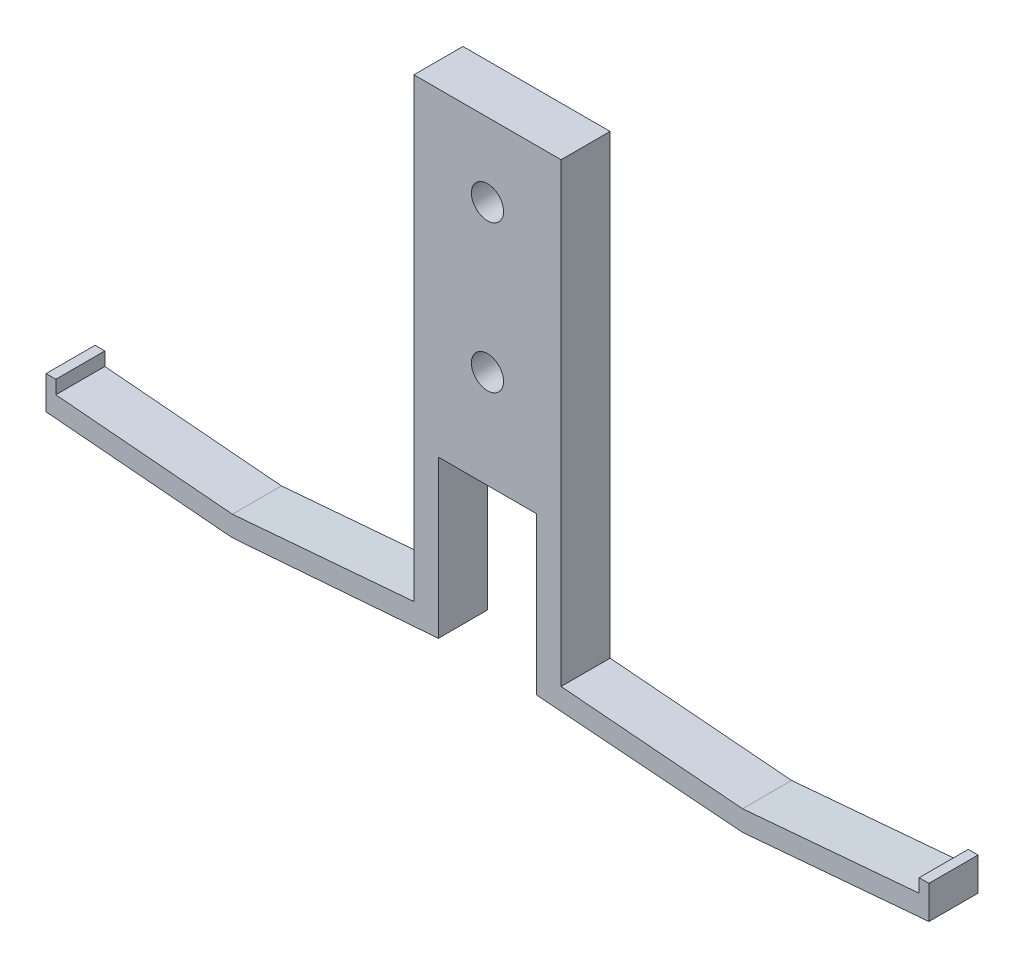
SolidWorks part; units mm, degrees
material "Nylon 6/10"
ref_plane "Front Plane" through (0, 0, 0) normal (0, 0, 1) x (1, 0, 0)
ref_plane "Top Plane" through (0, 0, 0) normal (0, 1, 0) x (1, 0, 0)
ref_plane "Right Plane" through (0, 0, 0) normal (1, 0, 0) x (0, 0, -1)
sketch "Sketch2" plane through (0, 0, 0) normal (0, 0, 1) x (1, 0, 0)
  line L1 (12.7, 0) -> (12.7, -40.64)
  line L2 (12.7, -40.64) -> (66.04, -44.7734)
  line L3 (66.04, -44.7734) -> (114.3, -40.64)
  line L4 (114.3, -40.64) -> (114.3, -32.0734)
  line L5 (111.76, -32.0734) -> (111.76, -35.56)
  line L6 (111.76, -35.56) -> (66.04, -39.4758)
  line L19 (114.3, -32.0734) -> (111.76, -32.0734)
  line L20 (0, 125.2351) -> (0, -75.9356) construction
  line L21 (12.7, 0) -> (-12.7, 0)
  line L22 (0, 0) -> (0, 82.55)
  line L23 (19.05, 82.55) -> (-19.05, 82.55)
  line L24 (19.05, 82.55) -> (19.05, 0)
  line L25 (19.05, 0) -> (19.05, -35.56)
  line L26 (19.05, -35.56) -> (66.04, -39.4758)
  line L27 (-19.05, 0) -> (-19.05, -35.56)
  line L28 (-19.05, 82.55) -> (-19.05, 0)
  line L29 (-12.7, 0) -> (-12.7, -40.64)
  line L30 (-12.7, -40.64) -> (-66.04, -44.7734)
  line L31 (-66.04, -44.7734) -> (-114.3, -40.64)
  line L32 (-114.3, -40.64) -> (-114.3, -32.0734)
  line L33 (-114.3, -32.0734) -> (-111.76, -32.0734)
  line L34 (-111.76, -32.0734) -> (-111.76, -35.56)
  line L35 (-111.76, -35.56) -> (-66.04, -39.4758)
  line L36 (-19.05, -35.56) -> (-66.04, -39.4758)
  dimension "D1" = 19.05
  dimension "D2" = 12.7
  dimension "D3" = 35.56
  dimension "D4" = 3.9158
  dimension "D5" = 40.64
  dimension "D6" = 2.54
  dimension "D7" = 45.72
  dimension "D8" = 46.99
  dimension "D9" = 12.7
  dimension "D10" = 82.55
extrude "Boss-Extrude1" add sketch "Sketch2" along normal blind 12.7 contours L26 L25 L24 L23 L22 L21 L1 L2 L3 L4 L19 L5 L6 | L27 L36 L35 L34 L33 L32 L31 L30 L29 L21 L22 L23 L28 region at (6.35, 1.711, 0) region at (-6.35, 1.711, 0)
hole_wizard "21/64 (0.32813) Diameter Hole1" positions "Sketch3" profile "Sketch4" hole size "21/64" standard "ANSI Inch" end condition through all
sketch "Sketch3" plane through (0, 0, 12.7) normal (0, 0, 1) x (1, 0, 0)
  point P0 (0, 25.4)
  point P2 (0, 63.5)
  dimension "D1" = 25.4
  dimension "D2" = 38.1
sketch "Sketch4" plane through (0, 25.4, 12.7) normal (1, 0, 0) x (0, -1, 0)
  line L0 (0, 0) -> (0, 12.7)
  line L1 (0, 12.7) -> (4.1673, 12.7)
  line L2 (4.1673, 12.7) -> (4.1673, 0)
  line L5 (4.1673, 0) -> (0, 0)
  line L11 (0, -6.35) -> (0, 107.95) construction
  dimension "Thru Hole Dia." = 8.3345
  dimension "Thru Hole Depth" = 12.7
